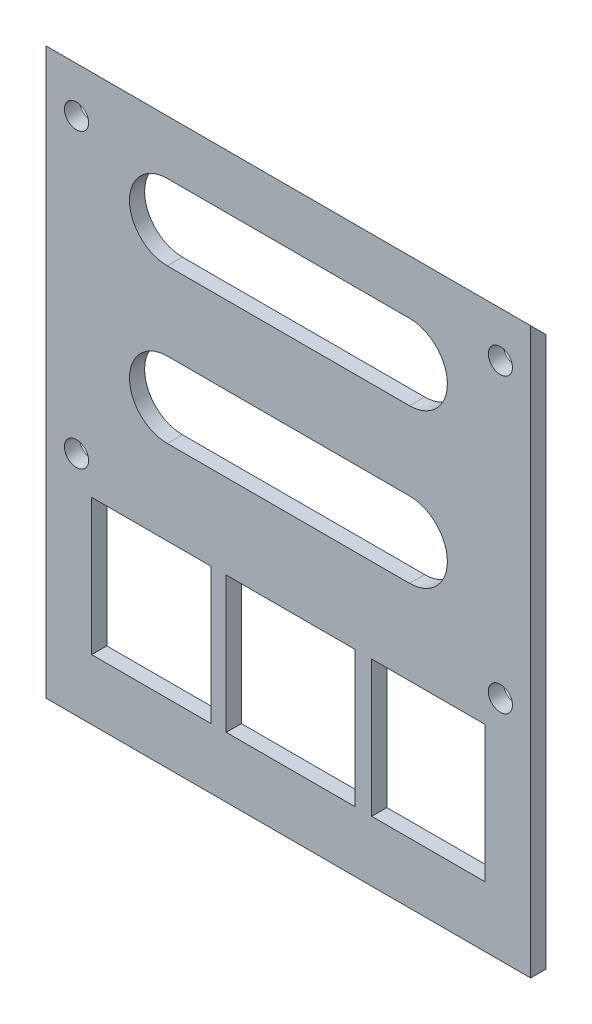
SolidWorks part; units mm, degrees
ref_plane "Płaszczyzna przednia" through (0, 0, 0) normal (0, 0, 1) x (1, 0, 0)
ref_plane "Płaszczyzna górna" through (0, 0, 0) normal (0, 1, 0) x (1, 0, 0)
ref_plane "Płaszczyzna prawa" through (0, 0, 0) normal (1, 0, 0) x (0, 0, -1)
sketch "Szkic1" plane through (0, 0, 0) normal (0, 0, 1) x (1, 0, 0)
  line L1 (0, 0) -> (64, 0)
  line L2 (0, 0) -> (0, 72.64)
  line L3 (0, 72.64) -> (64, 72.64)
  line L4 (64, 0) -> (64, 72.64)
  line L5 (64, 72.64) -> (0, 72.64)
  line L6 (64, 72.64) -> (64, 74.64)
  line L7 (64, 74.64) -> (0, 74.64)
  line L8 (0, 72.64) -> (0, 74.64)
  line L10 (6, 26) -> (58, 26)
  line L11 (6, 26) -> (6, 8)
  line L12 (6, 8) -> (58, 8)
  line L13 (58, 26) -> (58, 8)
extrude "Dodanie-wyciągnięcie1" add sketch "Szkic1" along normal blind 2 contours L1 L4 L3 L2 L10 L13 L12 L11 | L8 L3 L6 L7 region at (32, 41.1904, 0) region at (32, 73.64, 0)
chamfer "Sfazowanie1" distance 2 angle 45 1 edges at (32, 74.64, 0)
sketch "Szkic2" plane through (0, 0, 2) normal (0, 0, 1) x (1, 0, 0)
  line L0 (0, 8) -> (8, 8) construction
  line L1 (56, 34) -> (64, 26) construction
  line L2 (64, 72.64) -> (0, 72.64) construction
  line L3 (0, 0) -> (0, 74.64) construction
  line L4 (6, 8) -> (58, 8) construction
  line L5 (64, 8) -> (56, 8) construction
  line L6 (64, 0) -> (64, 74.64) construction
  line L7 (8, 0) -> (8, 26) construction
  line L8 (0, 0) -> (64, 0) construction
  line L9 (56, 0) -> (56, 26) construction
  line L10 (8, 26) -> (0, 26) construction
  line L11 (56, 26) -> (64, 26) construction
  line L12 (8, 26) -> (8, 34) construction
  line L13 (56, 26) -> (56, 34) construction
  line L14 (8, 34) -> (0, 26) construction
  line L16 (8, 72.64) -> (8, 64.64) construction
  line L17 (56, 72.64) -> (56, 64.64) construction
  line L18 (8, 64.64) -> (0, 72.64) construction
  line L19 (56, 64.64) -> (64, 72.64) construction
  circle A0 centre (4, 30) radius 1.6
  circle A1 centre (60, 30) radius 1.6
  circle A2 centre (4, 68.64) radius 1.6
  circle A3 centre (60, 68.64) radius 1.6
extrude "Wytnij-wyciągnięcie1" cut sketch "Szkic2" against normal blind 2
sketch "Szkic3" plane through (0, 0, 2) normal (0, 0, 1) x (1, 0, 0)
  line L0 (6, 26) -> (21.7834, 26)
  line L1 (6, 26) -> (58, 26) construction
  line L2 (21.7834, 26) -> (23.7834, 26)
  line L3 (23.7834, 26) -> (40.7834, 26)
  line L5 (43, 26) -> (58, 26)
  line L6 (6, 8) -> (58, 8) construction
  line L7 (21.7834, 26) -> (23.7834, 26)
  line L8 (21.7834, 26) -> (21.7834, 8)
  line L9 (21.7834, 8) -> (23.7834, 8)
  line L10 (23.7834, 26) -> (23.7834, 8)
  line L12 (43, 26) -> (40.7834, 26)
  line L13 (43, 26) -> (43, 8)
  line L14 (43, 8) -> (40.7834, 8)
  line L15 (40.7834, 26) -> (40.7834, 8)
  line M18 (6, 26) -> (58, 26)
  line M20 (58, 8) -> (6, 8)
extrude "Dodanie-wyciągnięcie2" add sketch "Szkic3" against normal blind 2 contours L15 L13 M18 M20 | L8 L7 L10 L9 region at (41.8917, 17, 2)
sketch "Szkic4" plane through (0, 0, 0) normal (0, 0, -1) x (-1, 0, 0)
  line L0 (-32, 32) -> (0, 32) construction
  line L1 (-41, 32) -> (-23, 32) construction
  line L2 (0, 0) -> (0, 72.64) construction
  line L3 (-32, 32) -> (-64, 32) construction
  line L4 (-64, 0) -> (-64, 72.64) construction
  line L5 (-32, 72.64) -> (0, 72.64) construction
  line L6 (0, 72.64) -> (-64, 72.64) construction
  line L7 (-32, 72.64) -> (-32, 32) construction
  line L8 (-32, 52.32) -> (0, 72.64) construction
  line L9 (-32, 52.32) -> (0, 32) construction
  line L10 (-32, 52.32) -> (-64, 32) construction
  line L11 (-32, 52.32) -> (-64, 72.64) construction
  line L12 (-48, 62.48) -> (-16, 62.48) construction
  line L13 (-48, 42.16) -> (-16, 42.16) construction
  line L14 (-48, 42.16) -> (-16, 42.16) construction
  line L15 (-48, 47.16) -> (-16, 47.16)
  line L16 (-48, 37.16) -> (-16, 37.16)
  line L17 (-48, 62.48) -> (-16, 62.48) construction
  line L18 (-48, 67.48) -> (-16, 67.48)
  line L19 (-48, 57.48) -> (-16, 57.48)
  arc A0 (-48, 47.16) -> (-48, 37.16) centre (-48, 42.16) ccw
  arc A1 (-16, 37.16) -> (-16, 47.16) centre (-16, 42.16) ccw
  arc A2 (-48, 67.48) -> (-48, 57.48) centre (-48, 62.48) ccw
  arc A3 (-16, 57.48) -> (-16, 67.48) centre (-16, 62.48) ccw
  point P21 (-32, 42.16)
  point P26 (-32, 62.48)
extrude "Wytnij-wyciągnięcie2" cut sketch "Szkic4" against normal blind 2
